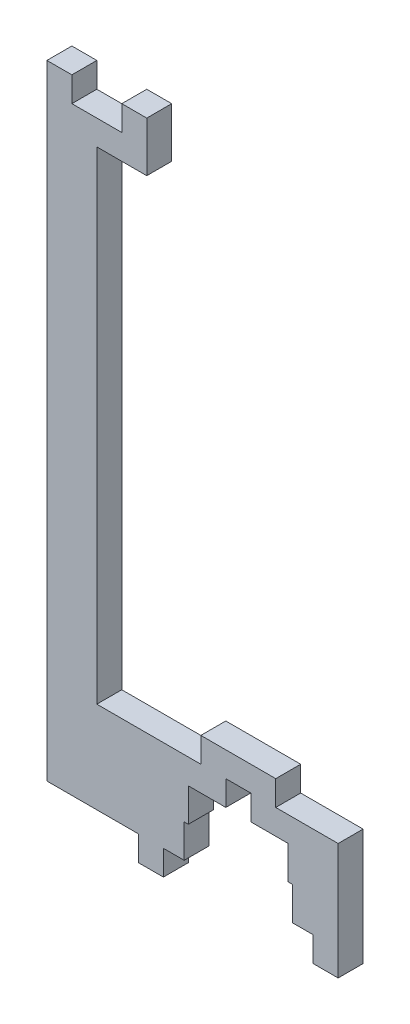
SolidWorks part; units mm, degrees
ref_plane "Alzado" through (0, 0, 0) normal (0, 0, 1) x (1, 0, 0)
ref_plane "Planta" through (0, 0, 0) normal (0, 1, 0) x (1, 0, 0)
ref_plane "Vista lateral" through (0, 0, 0) normal (1, 0, 0) x (0, 0, -1)
sketch "Croquis1" plane through (0, 0, 0) normal (0, 0, 1) x (1, 0, 0)
  line L17 (17, -65) -> (17, -61)
  line L18 (17, -61) -> (12.5, -61)
  line L19 (5, -61) -> (5, -65)
  line L21 (-12, -69) -> (-12, 3)
  line L24 (0, 0) -> (-6, 0)
  line L25 (-6, 0) -> (-6, -58)
  line L26 (-6, -58) -> (6.5, -58)
  line L27 (23, -58) -> (23, -69)
  line L30 (-12, 3) -> (-12, 6)
  line L31 (-12, 6) -> (-9, 6)
  line L32 (-9, 6) -> (-9, 3)
  line L35 (-12, -69) -> (-1, -69)
  line L36 (-1, -69) -> (-1, -72)
  line L37 (-1, -72) -> (2, -72)
  line L38 (2, -72) -> (2, -69)
  line L39 (2, -69) -> (4.5, -69)
  line L40 (17.5, -69) -> (20, -69)
  line L41 (20, -69) -> (20, -72)
  line L42 (20, -72) -> (23, -72)
  line L43 (23, -72) -> (23, -69)
  line L45 (-9, 3) -> (-3, 3)
  line L46 (-3, 3) -> (-3, 6)
  line L47 (-3, 6) -> (0, 6)
  line L48 (0, 6) -> (0, 0)
  line L49 (5, -65) -> (17, -65) construction
  line L50 (5, -65) -> (4.5, -65)
  line L51 (4.5, -65) -> (4.5, -69)
  line L52 (17, -65) -> (17.5, -65)
  line L53 (17.5, -65) -> (17.5, -69)
  line L54 (9.5, -61) -> (9.5, -58)
  line L55 (9.5, -58) -> (12.5, -58)
  line L56 (12.5, -58) -> (12.5, -61)
  line L57 (9.5, -61) -> (5, -61)
  line L59 (6.5, -58) -> (6.5, -55)
  line L60 (6.5, -55) -> (15.5, -55)
  line L61 (15.5, -58) -> (23, -58)
  line L62 (15.5, -55) -> (15.5, -58)
  point P5 (11, -58)
  dimension "D1" = 3
  dimension "D2" = 6
  dimension "D3" = 6
  dimension "D4" = 12
  dimension "D5" = 8
  dimension "D6" = 72
  dimension "D7" = 4
  dimension "D8" = 17
  dimension "D9" = 0.5
  dimension "D10" = 0.5
  dimension "D11" = 3
  dimension "D12" = 3
  dimension "D13" = 6
  dimension "D14" = 9
  dimension "D15" = 3
  dimension "D16" = 3
  dimension "D17" = 2.5
extrude "Saliente-Extruir1" add sketch "Croquis1" along normal blind 3
